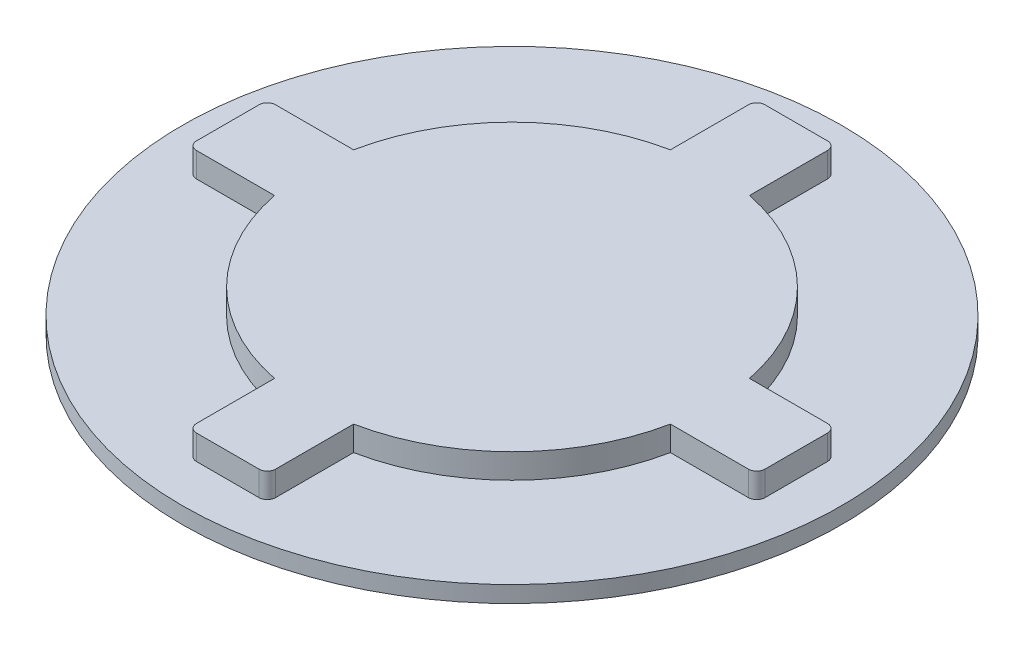
SolidWorks part; units mm, degrees
ref_plane "Alzado" through (0, 0, 0) normal (0, 0, 1) x (1, 0, 0)
ref_plane "Planta" through (0, 0, 0) normal (0, 1, 0) x (1, 0, 0)
ref_plane "Vista lateral" through (0, 0, 0) normal (1, 0, 0) x (0, 0, -1)
sketch "Croquis5" plane through (0, 0, 0) normal (0, 1, 0) x (1, 0, 0)
  circle A0 centre (0, 0) radius 24.5
  dimension "D1" = 49
extrude "Saliente-Extruir3" add sketch "Croquis5" along normal blind 3
sketch "Croquis6" plane through (0, 0, 0) normal (0, -1, 0) x (1, 0, 0)
  line L1 (33.5, 4.8) -> (-33.5, 4.8)
  line L2 (34.5, 3.8) -> (34.5, -3.8)
  line L3 (33.5, -4.8) -> (-33.5, -4.8)
  line L4 (-34.5, 3.8) -> (-34.5, -3.8)
  line L5 (34.5, 4.8) -> (-34.5, -4.8) construction
  line L6 (34.5, -4.8) -> (-34.5, 4.8) construction
  line L10 (3.8, -34.5) -> (-3.8, -34.5)
  line L11 (4.8, -33.5) -> (4.8, 33.5)
  line L12 (3.8, 34.5) -> (-3.8, 34.5)
  line L13 (-4.8, -33.5) -> (-4.8, 33.5)
  arc A0 (-3.8, -34.5) -> (-4.8, -33.5) centre (-3.8, -33.5) cw
  arc A1 (33.5, 4.8) -> (34.5, 3.8) centre (33.5, 3.8) cw
  arc A2 (34.5, -3.8) -> (33.5, -4.8) centre (33.5, -3.8) cw
  arc A3 (-33.5, -4.8) -> (-34.5, -3.8) centre (-33.5, -3.8) cw
  arc A4 (-33.5, 4.8) -> (-34.5, 3.8) centre (-33.5, 3.8) ccw
  arc A5 (4.8, -33.5) -> (3.8, -34.5) centre (3.8, -33.5) cw
  arc A6 (4.8, 33.5) -> (3.8, 34.5) centre (3.8, 33.5) ccw
  arc A7 (-4.8, 33.5) -> (-3.8, 34.5) centre (-3.8, 33.5) cw
  point P0 (0, 0)
  point P13 (0, 0)
  point P34 (0, 0)
  circle M5 centre (0, 0) radius 24.5
  dimension "D4" = 1
  dimension "D1" = 69
  dimension "D2" = 9.6
extrude "Saliente-Extruir4" add sketch "Croquis6" against normal blind 3 contours L1 L4 L3 M5 | M5 | L3 L2 L1 M5 | M5 region at (29.3987, 0, 0) region at (0, 0, 29.3987) region at (-29.3987, 0, 0) region at (0, 0, -29.3987)
sketch "Croquis7" plane through (0, 0, 0) normal (0, -1, 0) x (1, 0, 0)
  circle A0 centre (0, 0) radius 40
  dimension "D1" = 80
extrude "Saliente-Extruir5" add sketch "Croquis7" along normal blind 2
sketch "Croquis8" plane through (0, -2, 0) normal (0, -1, 0) x (1, 0, 0)
  line L0 (2.5, -25) -> (-2.5, -25)
  line L1 (25, 2.5) -> (-25, 2.5)
  line L2 (25, 2.5) -> (25, -2.5)
  line L3 (25, -2.5) -> (-25, -2.5)
  line L4 (-25, 2.5) -> (-25, -2.5)
  line L5 (25, 2.5) -> (-25, -2.5) construction
  line L6 (25, -2.5) -> (-25, 2.5) construction
  line L7 (2.5, -25) -> (2.5, 25)
  line L8 (2.5, 25) -> (-2.5, 25)
  line L9 (-2.5, -25) -> (-2.5, 25)
  circle A0 centre (0, 0) radius 15
  circle A1 centre (0, 0) radius 20
  point P0 (0, 0)
  point P13 (0, 0)
  dimension "D3" = 30
  dimension "D4" = 40
  dimension "D1" = 50
  dimension "D2" = 5
extrude "Cortar-Extruir3" cut sketch "Croquis8" against normal blind 2 contours A1 L9 L0 L7 | L9 A1 L7 A0 | L9 A0 L7 L3 | L9 L3 L7 L1 | L7 A0 L9 L1 | L7 A1 L9 A0 | A1 L7 L8 L9 | L3 A0 L1 L7 | L3 A1 L1 A0 | A1 L3 L2 L1 | L1 A0 L3 L9 | L1 A1 L3 A0 | A1 L1 L4 L3 | L9 A1 L1 A0 | L1 A1 L7 A0 | L7 A1 L3 A0 | L3 A1 L9 A0 region at (0, -2, -22.4737) region at (0, -2, -17.4389) region at (11.6344, -2, -11.6344) region at (-11.6344, -2, -11.6344) region at (0, -2, -8.7153) region at (22.4737, -2, 0) region at (17.4389, -2, 0) region at (-17.4389, -2, 0) region at (-22.4737, -2, 0) region at (8.7153, -2, 0) region at (0, -2, 0) region at (-8.7153, -2, 0) region at (-11.6344, -2, 11.6344) region at (0, -2, 8.7153) region at (11.6344, -2, 11.6344) region at (0, -2, 17.4389) region at (0, -2, 22.4737)
sketch "Croquis9" plane through (0, 0, 0) normal (0, -1, 0) x (1, 0, 0)
  line L0 (-25, 0) -> (25, 0) construction
  line L1 (-25, 2.5) -> (-25, -2.5) construction
  line L2 (25, 2.5) -> (25, -2.5) construction
  line L3 (0, -25) -> (0, 25) construction
  line L4 (2.5, -25) -> (-2.5, -25) construction
  line L5 (2.5, 25) -> (-2.5, 25) construction
  circle A0 centre (0, 0) radius 22.5 construction
  circle A1 centre (0, 0) radius 2
  dimension "D1" = 45
  dimension "4" = 4
extrude "Cortar-Extruir4" cut sketch "Croquis9" against normal blind 1
sketch "Croquis10" plane through (0, 0, 0) normal (0, -1, 0) x (1, 0, 0)
  line L0 (-25, 0) -> (25, 0) construction
  line L1 (-25, 2.5) -> (-25, -2.5) construction
  line L2 (25, 2.5) -> (25, -2.5) construction
  line L3 (0, 25) -> (0, -25) construction
  line L4 (2.5, 25) -> (-2.5, 25) construction
  line L5 (2.5, -25) -> (-2.5, -25) construction
  circle A0 centre (0, 0) radius 22.5 construction
  circle A1 centre (-22.5, 0) radius 0.5
  circle A2 centre (0, 22.5) radius 0.5
  circle A3 centre (22.5, 0) radius 0.5
  circle A4 centre (0, -22.5) radius 0.5
  point P26 (0, 0)
  dimension "D1" = 45
  dimension "D2" = 1
  dimension "D3" = 4
extrude "Cortar-Extruir5" cut sketch "Croquis10" against normal blind 2
